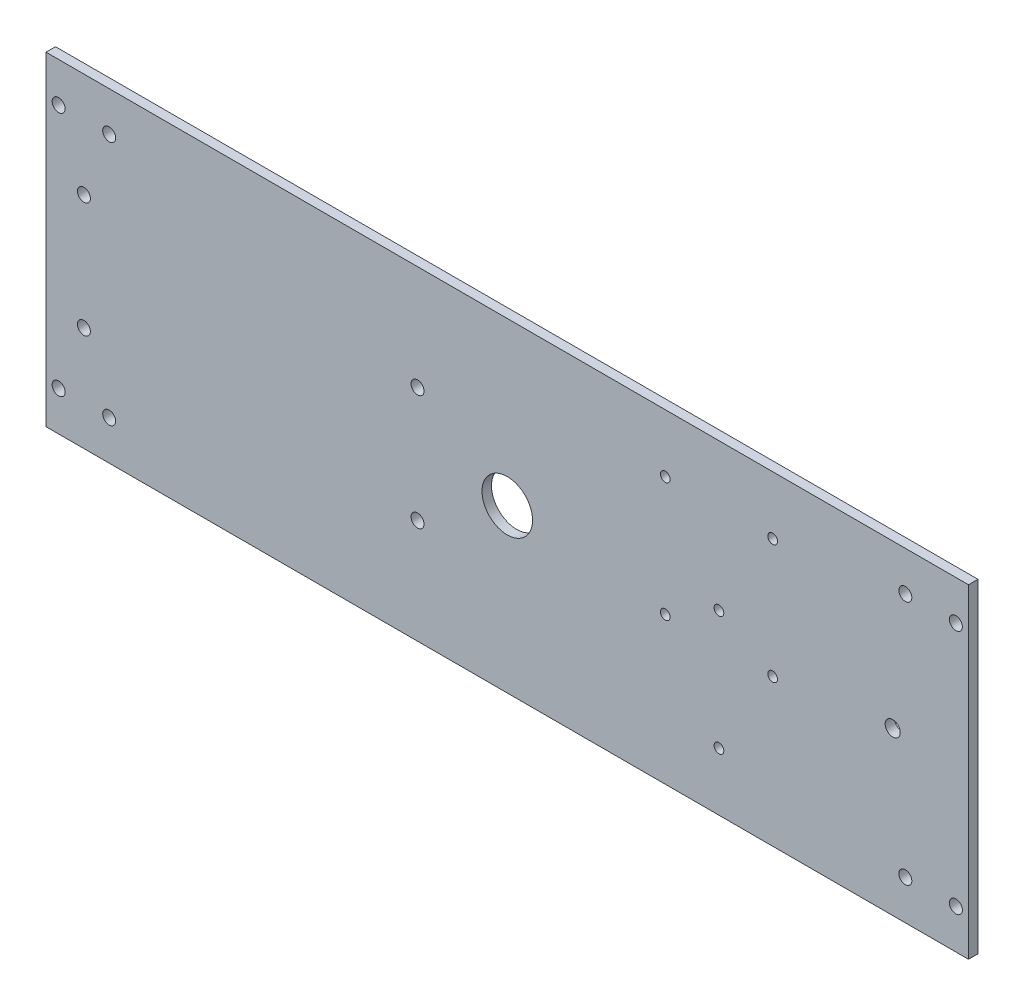
SolidWorks part; units mm, degrees
material "E-Glass Fiber"
ref_plane "Front Plane" through (0, 0, 0) normal (0, 0, 1) x (1, 0, 0)
ref_plane "Top Plane" through (0, 0, 0) normal (0, 1, 0) x (1, 0, 0)
ref_plane "Right Plane" through (0, 0, 0) normal (1, 0, 0) x (0, 0, -1)
sketch "Sketch1" plane through (0, 0, 0) normal (0, 0, 1) x (1, 0, 0)
  line L1 (-115.8875, -40.748) -> (115.8875, -40.748)
  line L2 (-115.8875, -40.748) -> (-115.8875, 40.7479)
  line L3 (-115.8875, 40.7479) -> (115.8875, 40.7479)
  line L4 (115.8875, -40.748) -> (115.8875, 40.7479)
  line L5 (-115.8875, -40.748) -> (115.8875, 40.7479) construction
  line L6 (-115.8875, 40.7479) -> (115.8875, -40.748) construction
  point P0 (0, 0)
  dimension "D1" = 231.775
  dimension "D2" = 81.4959
extrude "Boss-Extrude1" add sketch "Sketch1" along normal blind 2.3813
sketch "Sketch2" plane through (0, 0, 2.3813) normal (0, 0, 1) x (1, 0, 0)
  line L0 (-8.9154, 28.575) -> (29.1846, 28.575) construction
  line L1 (115.8875, 0) -> (111.125, 0) construction
  line L2 (115.8875, -40.748) -> (115.8875, 40.7479) construction
  line L3 (111.125, 0) -> (111.125, 9.525) construction
  line L4 (111.125, 9.525) -> (111.125, 25.4) construction
  line L5 (-115.8875, 0) -> (-111.125, 0) construction
  line L6 (-115.8875, 40.7479) -> (-115.8875, -40.748) construction
  line L7 (-111.125, 0) -> (-111.125, 9.525) construction
  line L8 (-111.125, 9.525) -> (-111.125, 25.4) construction
  line L9 (-115.8875, 30.8204) -> (-112.7125, 30.8204) construction
  line L10 (-112.7125, 30.8204) -> (-100.0125, 30.8204) construction
  line L11 (115.8875, 0) -> (96.8375, 0) construction
  dimension "D1" = 38.1
  dimension "D2" = 28.575
  dimension "D3" = 8.9154
  dimension "D4" = 4.7625
  dimension "D5" = 9.525
  dimension "D6" = 25.4
  dimension "D7" = 30.8204
  dimension "D8" = 12.7
  dimension "D9" = 3.175
  dimension "D10" = 19.05
hole_wizard "#4 Clearance Hole2" positions "Sketch6" profile "Sketch7" hole size "#4" standard "ANSI Inch" end condition through all
sketch "Sketch6" plane through (0, 0, 2.3813) normal (0, 0, 1) x (1, 0, 0)
  point P0 (-112.7125, 30.8204)
  point P3 (-100.0125, 30.8204)
sketch "Sketch7" plane through (-112.7125, 30.8204, 2.3813) normal (1, 0, 0) x (0, -1, 0)
  line L0 (0, 0) -> (0, 2.3813)
  line L1 (0, 2.3813) -> (1.6319, 2.3813)
  line L2 (1.6319, 2.3813) -> (1.6319, 0)
  line L5 (1.6319, 0) -> (0, 0)
  line L11 (0, -6.35) -> (0, 107.95) construction
  dimension "Thru Hole Dia." = 3.2639
  dimension "Thru Hole Depth" = 2.3813
mirror "Mirror2" about plane through (0, 0, 0) normal (1, 0, 0) of "#4 Clearance Hole2"
mirror "Mirror3" about plane through (0, 0, 0) normal (0, 1, 0) of "Mirror2"
hole_wizard "1/2 (0.5) Diameter Hole1" positions "Sketch9" profile "Sketch8" hole size "1/2" standard "ANSI Inch" end condition through all
sketch "Sketch9" plane through (0, 0, 2.3813) normal (0, 0, 1) x (1, 0, 0)
  point P0 (0, 0)
sketch "Sketch8" plane through (0, 0, 2.3813) normal (1, 0, 0) x (0, -1, 0)
  line L0 (0, 0) -> (0, 2.3812)
  line L1 (0, 2.3812) -> (6.35, 2.3812)
  line L2 (6.35, 2.3812) -> (6.35, 0)
  line L5 (6.35, 0) -> (0, 0)
  line L11 (0, -6.35) -> (0, 107.95) construction
  dimension "Thru Hole Dia." = 12.7
  dimension "Thru Hole Depth" = 2.3813
sketch "Sketch10" plane through (0, 0, 2.3813) normal (0, 0, 1) x (1, 0, 0)
  line L0 (0, 0) -> (-64.4525, 0) construction
  line L1 (-106.3625, -14.478) -> (-22.5425, -14.478) construction
  line L2 (-106.3625, -14.478) -> (-106.3625, 14.478) construction
  line L3 (-106.3625, 14.478) -> (-22.5425, 14.478) construction
  line L4 (-22.5425, -14.478) -> (-22.5425, 14.478) construction
  line L5 (-106.3625, -14.478) -> (-22.5425, 14.478) construction
  line L6 (-106.3625, 14.478) -> (-22.5425, -14.478) construction
  line L7 (-115.8875, 40.7479) -> (-115.8875, -40.748) construction
  line L8 (39.697, 26.162) -> (66.6718, 26.162) construction
  line L9 (53.1844, 26.162) -> (53.1844, 3.81) construction
  line L10 (0, 0) -> (53.1844, 0) construction
  line L11 (53.1844, 0) -> (53.1844, 3.81) construction
  point P0 (-64.4525, 0)
  dimension "D1" = 83.82
  dimension "D2" = 28.956
  dimension "D3" = 9.525
  dimension "D4" = 13.4874
  dimension "D5" = 22.352
  dimension "D6" = 26.9748
  dimension "D7" = 3.81
hole_wizard "#4 Clearance Hole3" positions "Sketch12" profile "Sketch13" hole size "#4" standard "ANSI Inch" end condition through all
sketch "Sketch12" plane through (0, 0, 2.3813) normal (0, 0, 1) x (1, 0, 0)
  point P0 (-106.3625, 14.478)
  point P3 (-22.5425, 14.478)
  point P6 (-22.5425, -14.478)
  point P9 (-106.3625, -14.478)
sketch "Sketch13" plane through (-106.3625, 14.478, 2.3813) normal (1, 0, 0) x (0, -1, 0)
  line L0 (0, 0) -> (0, 2.3813)
  line L1 (0, 2.3813) -> (1.6319, 2.3813)
  line L2 (1.6319, 2.3813) -> (1.6319, 0)
  line L5 (1.6319, 0) -> (0, 0)
  line L11 (0, -6.35) -> (0, 107.95) construction
  dimension "Thru Hole Dia." = 3.2639
  dimension "Thru Hole Depth" = 2.3813
hole_wizard "#2 Clearance Hole1" positions "Sketch15" profile "Sketch16" hole size "#2" standard "ANSI Inch" end condition through all
sketch "Sketch15" plane through (0, 0, 2.3813) normal (0, 0, 1) x (1, 0, 0)
  point P0 (53.1844, 3.81)
  point P3 (39.697, 26.162)
  point P6 (66.6718, 26.162)
sketch "Sketch16" plane through (53.1844, 3.81, 2.3813) normal (1, 0, 0) x (0, -1, 0)
  line L0 (0, 0) -> (0, 2.3813)
  line L1 (0, 2.3813) -> (1.2192, 2.3813)
  line L2 (1.2192, 2.3813) -> (1.2192, 0)
  line L5 (1.2192, 0) -> (0, 0)
  line L11 (0, -6.35) -> (0, 107.95) construction
  dimension "Thru Hole Dia." = 2.4384
  dimension "Thru Hole Depth" = 2.3813
pattern_linear "LPattern1" count 2 spacing 29.972 along (0, -1, 0) of "#2 Clearance Hole1"
hole_wizard "#6 Clearance Hole1" positions "Sketch18" profile "Sketch17" hole size "#6" standard "ANSI Inch" end condition through all
sketch "Sketch18" plane through (0, 0, 2.3813) normal (0, 0, 1) x (1, 0, 0)
  point P0 (96.8375, 0)
sketch "Sketch17" plane through (96.8375, 0, 2.3813) normal (1, 0, 0) x (0, -1, 0)
  line L0 (0, 0) -> (0, 2.3812)
  line L1 (0, 2.3812) -> (1.8986, 2.3812)
  line L2 (1.8986, 2.3812) -> (1.8986, 0)
  line L5 (1.8986, 0) -> (0, 0)
  line L11 (0, -6.35) -> (0, 107.95) construction
  dimension "Thru Hole Dia." = 3.7973
  dimension "Thru Hole Depth" = 2.3813
